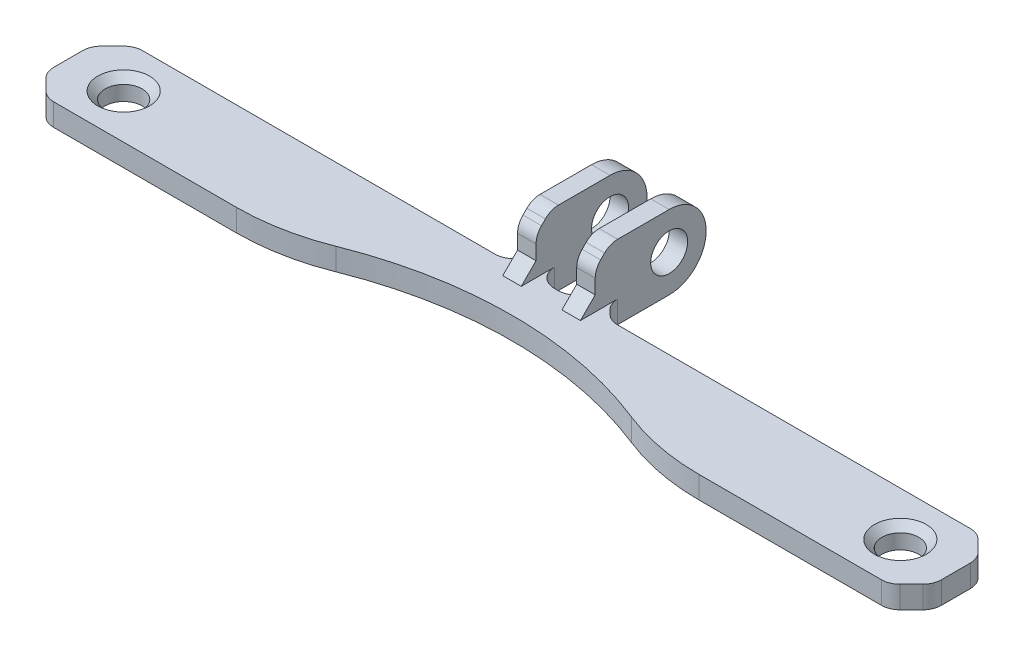
SolidWorks part; units mm, degrees
ref_plane "Front" through (0, 0, 0) normal (0, 0, 1) x (1, 0, 0)
ref_plane "Top" through (0, 0, 0) normal (0, 1, 0) x (1, 0, 0)
ref_plane "Right" through (0, 0, 0) normal (1, 0, 0) x (0, 0, -1)
sketch "Sketch2" plane through (0, 0, 0) normal (0, 1, 0) x (1, 0, 0)
  line L3 (60, 0) -> (-60, 0)
  line L7 (-60, 0) -> (-60, -12)
  line L15 (0, 0) -> (0, -120) construction
  line L19 (60, -12) -> (24.7386, -12)
  line L20 (60, 0) -> (60, -12)
  line L21 (-52.5, -120) -> (52.5, -120) construction
  line L22 (-24.7386, -12) -> (-60, -12)
  circle A0 centre (-52.5, -6) radius 2.5
  circle A3 centre (52.5, -6) radius 2.5
  arc A4 (24.7386, -12) -> (-24.7386, -12) centre (0, -60) ccw
  point P18 (0, 0)
  dimension "D5" = 5
  dimension "D4" = 105
  dimension "D6" = 54
  dimension "D1" = 120
  dimension "D2" = 12
  dimension "D3" = 120
  dimension "D7" = 6
extrude "Boss-Extrude1" add sketch "Sketch2" along normal blind 3 contours L20 L3 L7 L19 A0 A3 | L15 L3 L7 L19 A0 region at (0, 0, 5.4016)
sketch "Sketch3" plane through (0, 0, 0) normal (1, 0, 0) x (0, 0, -1)
  line L1 (0, 0) -> (15, 0)
  line L2 (0, 0) -> (0, 10)
  line L3 (0, 10) -> (15, 10)
  line L4 (15, 0) -> (15, 10)
  dimension "D1" = 10
  dimension "D2" = 15
extrude "Boss-Extrude2" add sketch "Sketch3" along normal blind 2.5 from offset 2.75
fillet "Fillet2" 2 edges at (4, 10, -15) (4, 0, -15) type full round first side face at (4, 10, -7.5) second side face at (1.6, 0, 1.2) middle face at (4, 5, -15)
mirror "Mirror1" about plane through (0, 0, 0) normal (1, 0, 0) of "Fillet2", "Boss-Extrude2"
chamfer "Chamfer1" distance 2 angle 45 2 edges at (4, 3, 0) (-4, 3, 0)
chamfer "Chamfer2" distance 2 angle 45 4 edges at (-5.25, 1.5, 0) (5.25, 1.5, 0) (4, 10, 0) (-4, 10, 0)
sketch "Sketch5" plane through (5.25, 0, 0) normal (1, 0, 0) x (0, 0, -1)
  circle A0 centre (10, 5) radius 2.5
  dimension "D1" = 5
extrude "Cut-Extrude2" cut sketch "Sketch5" against normal through all
chamfer "Chamfer3" distance 3 angle 45 4 edges at (-60, 1.5, 0) (60, 1.5, 0) (60, 1.5, 12) (-60, 1.5, 12)
fillet "Fillet3" radius 2.5 18 edges at (-57, 1.5, 0) (-7.25, 1.5, 0) (-5.25, 1.5, -2) (-2.75, 1.5, 0) (2.75, 1.5, 0) (5.25, 1.5, -2) (7.25, 1.5, 0) (57, 1.5, 0) (60, 1.5, 3) (60, 1.5, 9) (57, 1.5, 12) (-60, 1.5, 3) (4, 8, 0) (4, 10, -2) (-4, 10, -2) (-4, 8, 0) (-60, 1.5, 9) (-57, 1.5, 12)
chamfer "Chamfer4" distance 1 angle 45 2 edges at (52.5, 3, 8.5) (-52.5, 3, 8.5)
fillet "Fillet4" radius 30.5 2 edges at (24.7386, 1.5, 12) (-24.7386, 1.5, 12)
